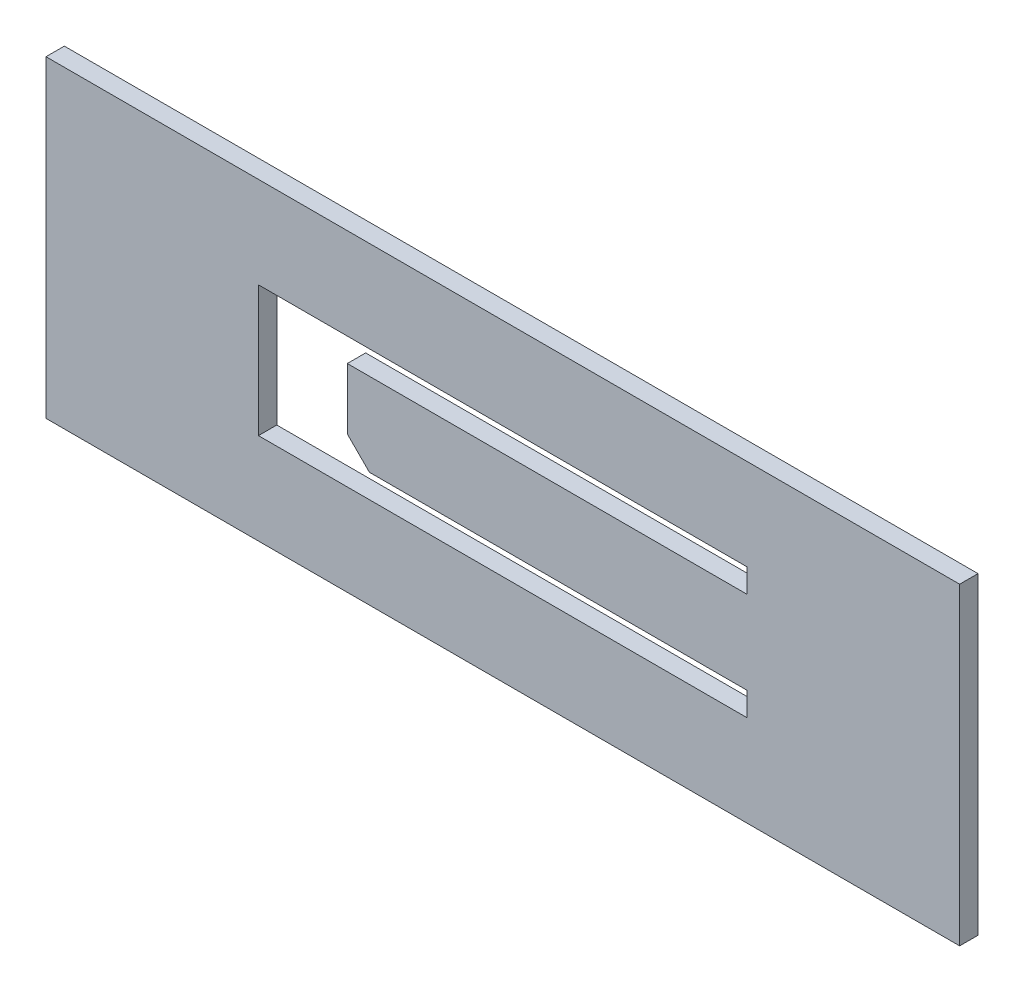
SolidWorks part; units mm, degrees
ref_plane "Спереди" through (0, 0, 0) normal (0, 0, 1) x (1, 0, 0)
ref_plane "Сверху" through (0, 0, 0) normal (0, 1, 0) x (1, 0, 0)
ref_plane "Справа" through (0, 0, 0) normal (1, 0, 0) x (0, 0, -1)
sketch "Эскиз1_fr" plane through (0, 0, 0) normal (0, 0, 1) x (1, 0, 0)
  line L0 (74.6378, -25.5901) -> (-74.6378, -25.5901)
  line L1 (74.6378, -25.5901) -> (74.6378, 25.5901)
  line L2 (-74.6378, -25.5901) -> (-74.6378, 25.5901)
  line L3 (74.6378, 25.5901) -> (-74.6378, 25.5901)
  line L4 (74.6378, -25.5901) -> (-74.6378, 25.5901) construction
  line L5 (-74.6378, -25.5901) -> (74.6378, 25.5901) construction
  line L6 (39.9265, -10.6721) -> (-39.9265, -10.6721)
  line L7 (39.9265, -10.6721) -> (39.9265, -6.792)
  line L8 (-39.9265, -10.6721) -> (-39.9265, 10.6721)
  line L9 (39.9265, 10.6721) -> (-39.9265, 10.6721)
  line L10 (39.9265, -10.6721) -> (-39.9265, 10.6721) construction
  line L11 (-39.9265, -10.6721) -> (39.9265, 10.6721) construction
  line L12 (39.9265, 6.792) -> (39.9265, 10.6721)
  line L13 (39.9265, 6.792) -> (-25.4101, 6.792)
  line L15 (39.9265, -6.792) -> (-21.7954, -6.792)
  line L16 (-25.4101, 6.792) -> (-25.4101, -3.1773)
  line L17 (-21.7954, -6.792) -> (-25.4101, -3.1773)
  point P1 (0, 0)
  point P2 (0, 0)
  dimension "D1" = 5.1119
base flange "Базовая кромка1" sketch "Эскиз1_fr" thickness 3 reverse thickness direction no parameters "D1"=1
sketch "Сгиб-Линии1" plane through (0, 0, 0) normal (0, 1, 0) x (1, 0, 0)
sketch "Граничная рамка1" plane through (0, 0, 0) normal (0, 1, 0) x (1, 0, 0)
sheet metal parameters "Листовой металл3" thickness 3 parameters "D1"=1
flat pattern "Развертка3" [suppressed]
sketch "Сгиб-Линии2" plane through (0, 0, 0) normal (0, 1, 0) x (1, 0, 0)
sketch "Граничная рамка2" [suppressed] plane through (0, 0, 0) normal (0, 1, 0) x (1, 0, 0)
